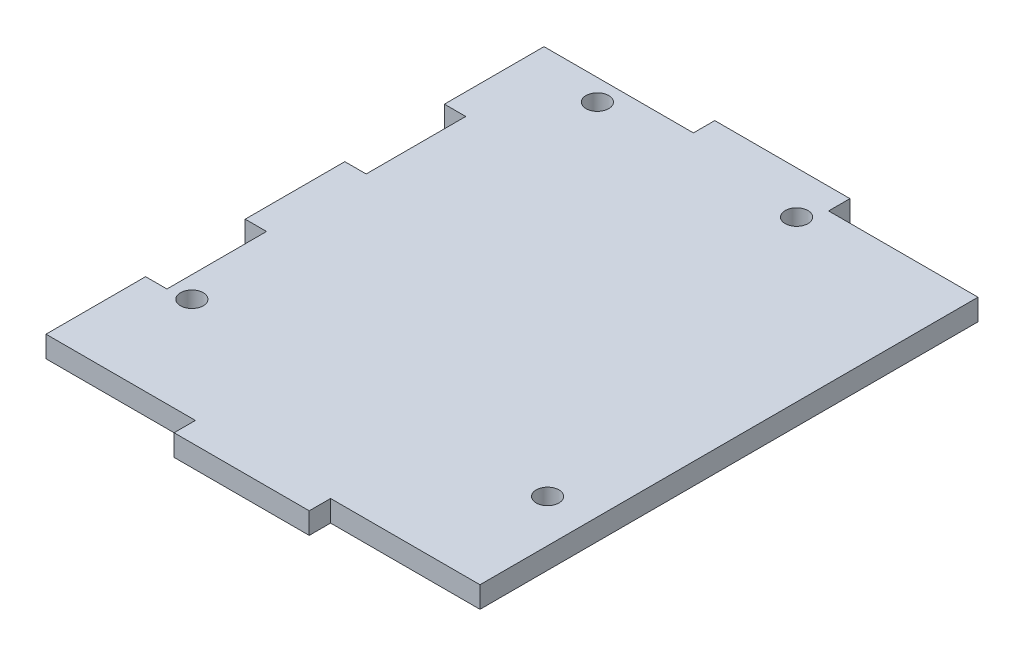
SolidWorks part; units mm, degrees
ref_plane "Front Plane" through (0, 0, 0) normal (0, 0, 1) x (1, 0, 0)
ref_plane "Top Plane" through (0, 0, 0) normal (0, 1, 0) x (1, 0, 0)
ref_plane "Right Plane" through (0, 0, 0) normal (1, 0, 0) x (0, 0, -1)
sketch "Sketch1" plane through (0, 0, 0) normal (0, 1, 0) x (1, 0, 0)
  line L0 (0, -7) -> (0, 7)
  line L1 (0, 7) -> (3, 7)
  line L2 (3, 7) -> (3, 21)
  line L3 (3, 21) -> (0, 21)
  line L4 (0, 21) -> (0, 35)
  line L5 (0, 35) -> (3, 35)
  line L6 (57.5, 34.5) -> (57.5, -34.5)
  line L7 (3, 35) -> (21, 35)
  line L8 (21, 35) -> (21, 38)
  line L9 (21, 38) -> (40, 38)
  line L10 (40, 38) -> (40, 35)
  line L11 (40, 35) -> (58, 35)
  line L12 (3.5, -34.5) -> (57.5, -34.5)
  line L13 (0, 0) -> (58, 0) construction
  line L14 (61, 21) -> (61, -21)
  line L17 (61, -21) -> (61, -35)
  line L18 (61, -35) -> (58, -35)
  line L19 (61, 35) -> (58, 35)
  line L20 (0, -35) -> (3, -35)
  line L21 (0, -21) -> (0, -35)
  line L22 (3, -21) -> (0, -21)
  line L23 (3, -7) -> (3, -21)
  line L24 (0, -7) -> (3, -7)
  line L25 (30.5, -34.5) -> (30.5, 34.5) construction
  line L26 (61, 21) -> (61, 35)
  line L27 (3.5, 34.5) -> (57.5, 34.5)
  line L28 (3.5, 34.5) -> (3.5, -34.5)
  line L29 (3.5, -34.5) -> (57.5, -34.5)
  line L30 (57.5, 34.5) -> (57.5, -34.5)
  line L31 (3.5, 34.5) -> (57.5, -34.5) construction
  line L32 (3.5, -34.5) -> (57.5, 34.5) construction
  line L37 (61, -35) -> (58, -35)
  line L38 (40, -35) -> (58, -35)
  line L39 (40, -38) -> (40, -35)
  line L40 (21, -38) -> (40, -38)
  line L41 (21, -35) -> (21, -38)
  line L42 (3, -35) -> (21, -35)
  line L43 (0, -35) -> (3, -35)
  circle A0 centre (6, -20.5) radius 1.6
  circle A1 centre (55, -19.5) radius 1.6
  circle A2 centre (10.5, 32) radius 1.6
  circle A3 centre (38.5, 32) radius 1.6
  point P29 (30.5, 0)
  dimension "D14" = 3.2
  dimension "D17" = 3.2
  dimension "D18" = 3.2
  dimension "D19" = 3.2
  dimension "D1" = 7
  dimension "D2" = 14
  dimension "D3" = 14
  dimension "D4" = 19
  dimension "D5" = 18
  dimension "D6" = 54
  dimension "D7" = 18
  dimension "D8" = 3
  dimension "D9" = 3
  dimension "D10" = 14
  dimension "D11" = 3
  dimension "D12" = 69
  dimension "D13" = 2.5
  dimension "D15" = 2.5
  dimension "D16" = 15
  dimension "D20" = 7
  dimension "D21" = 2.5
  dimension "D22" = 2.5
  dimension "D23" = 19
extrude "Boss-Extrude1" add sketch "Sketch1" along normal blind 3 contours L20 L42 L41 L40 L39 L38 L18 L17 L26 L19 L11 L10 L9 L8 L7 L5 L4 L3 L2 L1 L0 L24 L23 L22 L21 L28 L27 L6 L12 | L27 L28 L12 L6 A3 A2 A1 A0 region at (0.9745, 0, 0) region at (30.5261, 0, 0.0523)
